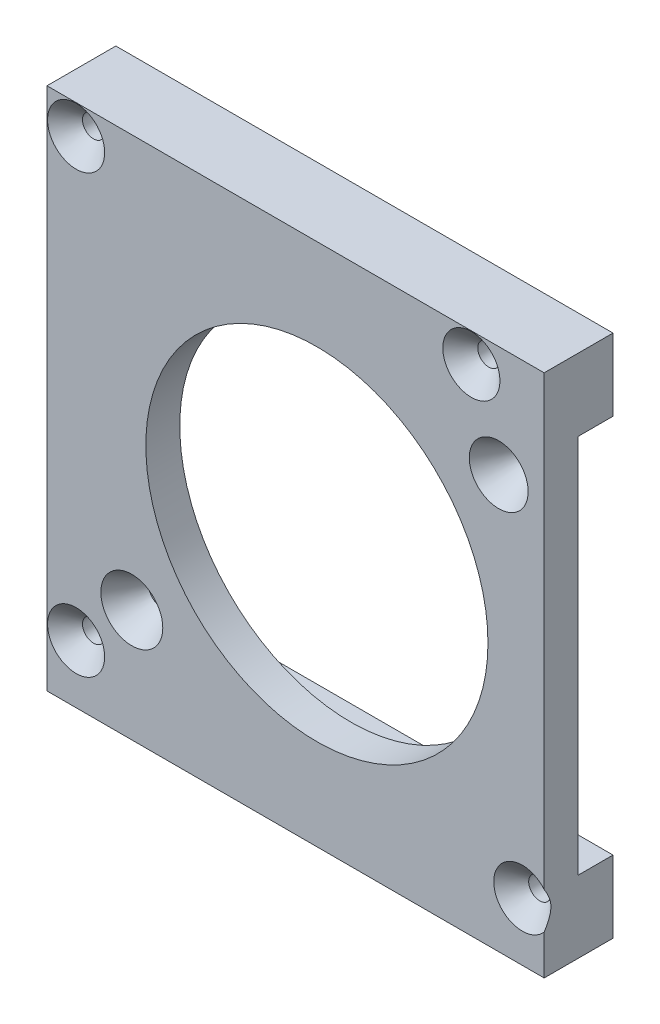
SolidWorks part; units mm, degrees
ref_plane "Front Plane" through (0, 0, 0) normal (0, 0, 1) x (1, 0, 0)
ref_plane "Top Plane" through (0, 0, 0) normal (0, 1, 0) x (1, 0, 0)
ref_plane "Right Plane" through (0, 0, 0) normal (1, 0, 0) x (0, 0, -1)
sketch "Sketch1" plane through (0, 0, 0) normal (0, 0, 1) x (1, 0, 0)
  line L0 (12.0169, 13.05) -> (16.575, 18) construction
  line L1 (-16.575, -18) -> (16.575, -18)
  line L2 (-16.575, -18) -> (-16.575, 18)
  line L3 (-16.575, 18) -> (16.575, 18)
  line L4 (16.575, -18) -> (16.575, -13.05)
  line L5 (-16.575, -18) -> (-12.0169, -13.05) construction
  line L6 (-16.575, 18) -> (-12.0169, 13.05) construction
  line L7 (16.575, 13.05) -> (16.575, 18)
  line L8 (-14.975, -13.05) -> (16.575, -13.05)
  line L9 (-14.975, -13.05) -> (-14.975, 13.05)
  line L10 (-14.975, 13.05) -> (16.575, 13.05)
  line L12 (12.0169, -13.05) -> (16.575, -18) construction
  point P0 (0, 0)
  dimension "D1" = 33.15
  dimension "D2" = 36
  dimension "D3" = 26.1
  dimension "D4" = 1.6
extrude "Boss-Extrude1" add sketch "Sketch1" along normal blind 2.4
sketch "Sketch2" plane through (0, 0, 2.4) normal (0, 0, 1) x (1, 0, 0)
  line L0 (-14.975, -13.05) -> (-14.975, 13.05) construction
  line L1 (-16.575, 18) -> (16.575, 18)
  line L2 (-16.575, 18) -> (-16.575, -18)
  line L3 (-16.575, -18) -> (16.575, -18)
  line L4 (16.575, 18) -> (16.575, -18)
  line L5 (-12.675, -10.2729) -> (-12.675, -9.8377) construction
  line L6 (-10.785, 0) -> (-10.785, 5.0525) construction
  line L9 (-11.7479, -11.2) -> (-10.1563, -11.2)
  line L10 (13.453, 11.2) -> (11.4356, 11.2) construction
  line L11 (14.275, 10.378) -> (14.275, 10.3258) construction
  line L12 (-14.975, 13.05) -> (16.575, 13.05) construction
  line L13 (16.575, -13.05) -> (-14.975, -13.05) construction
  circle A0 centre (0.965, 0) radius 11.75
  circle A1 centre (13.453, 10.378) radius 0.822
  circle A2 centre (-11.7479, -10.2729) radius 0.9271
  dimension "D1" = 23.5
  dimension "D2" = 4.19
  dimension "D3" = 2.3
  dimension "D4" = 2.3
  dimension "D5" = 1.85
  dimension "D6" = 1.85
extrude "Boss-Extrude2" add sketch "Sketch2" along normal blind 2.33
chamfer "Chamfer1" distance 1.2 angle 60 2 edges at (-10.8208, -10.2729, 4.73) (14.275, 10.378, 4.73) first distance on face at (0, 0, 4.73)
sketch "Sketch3" plane through (0, 0, 4.73) normal (0, 0, 1) x (1, 0, 0)
  line L0 (16.575, 18) -> (16.575, -18) construction
  line L1 (16.575, 18) -> (-16.575, 18) construction
  line L2 (-16.575, 18) -> (-16.575, -18) construction
  line L3 (-16.575, -18) -> (16.575, -18) construction
  circle A0 centre (-15.575, 16) radius 0.762
  circle A1 centre (11.575, 16) radius 0.762
  circle A2 centre (-15.575, -14) radius 0.762
  circle A3 centre (15.075, -14) radius 0.762
  point P19 (15.1015, -14.1755)
  dimension "D2" = 1.524
  dimension "D4" = 1.524
  dimension "D7" = 5
  dimension "D8" = 1.5
  dimension "D1" = 2
  dimension "D3" = 1
  dimension "D5" = 1
  dimension "D6" = 4
  dimension "D9" = 4
extrude "Cut-Extrude1" cut sketch "Sketch3" against normal blind 5.8
sketch "Sketch4" plane through (-16.575, 0, 0) normal (-1, 0, 0) x (0, 0, 1)
  line L1 (0, 18) -> (4.73, 18)
  line L2 (0, 18) -> (0, -18)
  line L3 (0, -18) -> (4.73, -18)
  line L4 (4.73, 18) -> (4.73, -18)
extrude "Boss-Extrude3" add sketch "Sketch4" along normal blind 1
chamfer "Chamfer2" distance 1.2 angle 45 4 edges at (-14.813, -14, 4.73) (14.313, -14, 4.73) (10.813, 16, 4.73) (-14.813, 16, 4.73)
